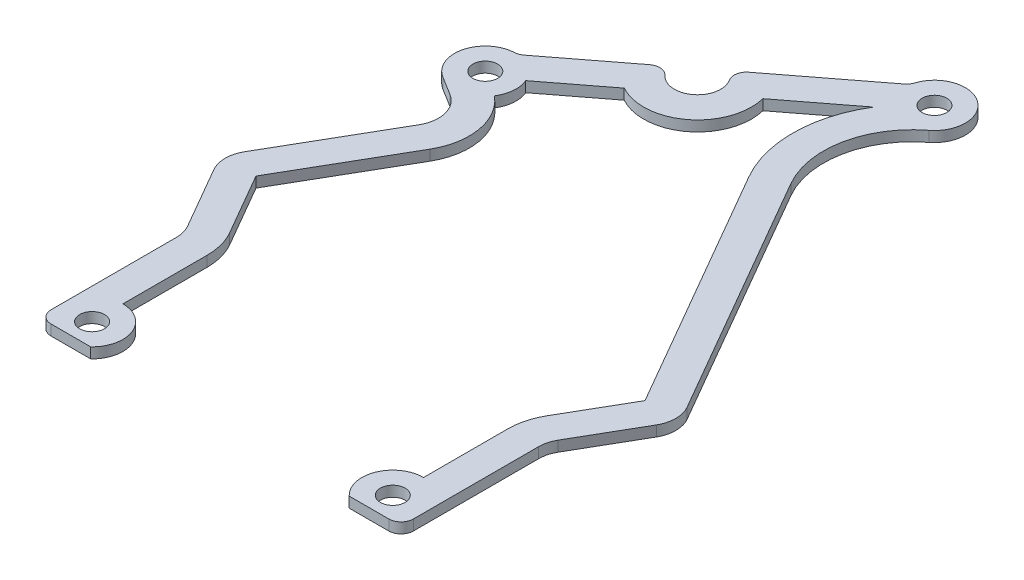
SolidWorks part; units mm, degrees
material "Alum Plate"
ref_plane "Front Plane" through (0, 0, 0) normal (0, 0, 1) x (1, 0, 0)
ref_plane "Top Plane" through (0, 0, 0) normal (0, 1, 0) x (1, 0, 0)
ref_plane "Right Plane" through (0, 0, 0) normal (1, 0, 0) x (0, 0, -1)
sketch "Top Layout" plane through (0, 0, 0) normal (0, 1, 0) x (1, 0, 0)
  line L0 (-114.046, -123.825) -> (-104.775, -123.825) construction
  line L1 (-104.775, -142.875) -> (-101.6, -142.875)
  line L2 (-104.775, -142.875) -> (-104.775, -104.775)
  line L3 (-104.775, -104.775) -> (-101.6, -104.775)
  line L4 (-101.6, -142.875) -> (-101.6, -104.775)
  line L5 (-104.775, -142.875) -> (-101.6, -104.775) construction
  line L6 (-104.775, -104.775) -> (-101.6, -142.875) construction
  line L7 (-19.05, -105.8164) -> (-101.6, -105.8164)
  line L8 (-19.05, -105.8164) -> (-19.05, -141.8336)
  line L9 (-19.05, -141.8336) -> (-101.6, -141.8336)
  line L10 (-101.6, -105.8164) -> (-101.6, -141.8336)
  line L11 (-19.05, -105.8164) -> (-101.6, -141.8336) construction
  line L12 (-19.05, -141.8336) -> (-101.6, -105.8164) construction
  line L13 (-133.096, -85.725) -> (-114.046, -85.725)
  line L14 (-133.096, -85.725) -> (-133.096, -161.925)
  line L15 (-133.096, -161.925) -> (-114.046, -161.925)
  line L16 (-114.046, -85.725) -> (-114.046, -161.925)
  line L17 (-133.096, -85.725) -> (-114.046, -161.925) construction
  line L18 (-133.096, -161.925) -> (-114.046, -85.725) construction
  line L19 (-104.775, -123.825) -> (0, -123.825) construction
  line L20 (0, -123.825) -> (0, 0) construction
  line L21 (-52.3528, -40.1717) -> (0, 0) construction
  line L22 (-70.6449, -16.3328) -> (-18.2922, 23.8388)
  line L23 (-34.0606, -64.0105) -> (18.2922, -23.8388)
  line L24 (-30.9251, 40.3023) -> (-122.2248, -29.7544)
  line L25 (-153.9748, -53.975) -> (-153.9748, -123.825)
  line L26 (-109.5248, -162.052) -> (109.5248, -162.052)
  line L27 (0, -162.052) -> (0, -123.825) construction
  line L28 (-109.5248, -162.052) -> (-109.5248, -20.0093) construction
  line L29 (-104.775, -142.875) -> (-104.775, -152.527)
  line L30 (-104.775, -152.527) -> (104.775, -152.527)
  line L31 (104.775, -104.775) -> (101.6, -104.775)
  line L32 (-144.4498, -73.025) -> (-109.5248, -73.025)
  line L33 (-144.4498, -73.025) -> (-144.4498, -123.825)
  line L34 (-144.4498, -123.825) -> (-109.5248, -123.825) construction
  line L35 (-109.5248, -73.025) -> (-109.5248, -162.052)
  line L36 (-144.4498, -73.025) -> (-109.5248, -123.825) construction
  line L37 (-144.4498, -123.825) -> (-109.5248, -73.025) construction
  line L38 (101.6, -142.875) -> (101.6, -104.775)
  line L39 (104.775, -142.875) -> (101.6, -142.875)
  line L40 (104.775, -142.875) -> (104.775, -104.775)
  line L41 (104.775, -142.875) -> (104.775, -152.527)
  line L42 (109.5248, -162.052) -> (109.5248, -20.0093) construction
  line L43 (30.9251, 40.3023) -> (122.2248, -29.7544)
  line L45 (19.05, -141.8336) -> (101.6, -141.8336)
  line L46 (101.6, -105.8164) -> (101.6, -141.8336)
  line L47 (19.05, -105.8164) -> (101.6, -105.8164)
  line L48 (19.05, -105.8164) -> (19.05, -141.8336)
  line L49 (133.096, -161.925) -> (114.046, -161.925)
  line L50 (114.046, -85.725) -> (114.046, -161.925)
  line L51 (133.096, -85.725) -> (114.046, -85.725)
  line L52 (133.096, -85.725) -> (133.096, -161.925)
  line L53 (144.4498, -123.825) -> (109.5248, -123.825) construction
  line L54 (109.5248, -73.025) -> (109.5248, -162.052)
  line L55 (144.4498, -73.025) -> (109.5248, -73.025)
  line L56 (144.4498, -73.025) -> (144.4498, -123.825)
  line L57 (-109.5248, -123.825) -> (-109.5248, -162.052) construction
  line L62 (-153.9748, -53.975) -> (-122.2248, -53.975)
  line L63 (-122.2248, -53.975) -> (-122.2248, -29.7544)
  line L64 (-144.4498, -123.825) -> (-153.9748, -123.825)
  line L65 (153.9748, -53.975) -> (153.9748, -123.825)
  line L66 (109.5248, -123.825) -> (109.5248, -162.052) construction
  line L67 (144.4498, -123.825) -> (153.9748, -123.825)
  line L68 (122.2248, -29.7544) -> (122.2248, -53.975)
  line L73 (-104.775, -104.775) -> (-104.775, -16.3647) construction
  line L74 (-95.25, -162.052) -> (-95.25, -9.0559) construction
  line L75 (-109.5248, -162.052) -> (-109.5248, -123.825) construction
  line L76 (109.5248, -162.052) -> (109.5248, -123.825) construction
  line L77 (122.2248, -53.975) -> (153.9748, -53.975)
  line L83 (104.775, -155.5496) -> (-104.775, -155.5496) construction
  line L88 (95.25, -162.052) -> (95.25, -9.0559) construction
  line L89 (104.775, -104.775) -> (104.775, -16.3647) construction
  line L92 (-104.775, -152.527) -> (-104.775, -162.052) construction
  line L93 (-14.605, -76.327) -> (14.605, -76.327)
  line L94 (-14.605, -76.327) -> (-14.605, -152.527)
  line L95 (-14.605, -152.527) -> (14.605, -152.527)
  line L96 (14.605, -76.327) -> (14.605, -152.527)
  line L97 (-14.605, -76.327) -> (14.605, -152.527) construction
  line L98 (-14.605, -152.527) -> (14.605, -76.327) construction
  line L99 (104.775, -152.527) -> (104.775, -162.052) construction
  line L100 (-19.05, -105.8164) -> (0, -105.8164) construction
  line L107 (0, -105.8164) -> (19.05, -105.8164) construction
  line L108 (104.775, -123.825) -> (114.046, -123.825) construction
  circle A0 centre (0, 0) radius 114.3
  circle A1 centre (0, 0) radius 6.35
  circle A2 centre (-52.3528, -40.1717) radius 17.8
  circle A3 centre (0, 0) radius 30.0482
  circle A4 centre (-52.3528, -40.1717) radius 30.0482
  arc A5 (-30.9251, 40.3023) -> (30.9251, 40.3023) centre (0, 0) cw
  point P2 (-103.1875, -123.825)
  point P7 (-60.325, -123.825)
  point P12 (-123.571, -123.825)
  point P30 (-126.9873, -98.425)
  point P35 (0, -114.427)
  point P53 (0, -152.527)
  dimension "D1" = 35.6
  dimension "D2" = 12.7
  dimension "D3" = 228.6
  dimension "D11" = 60.0964
  dimension "D12" = 50.8
  dimension "D14" = 52.5
  dimension "D4" = 3.175
  dimension "D5" = 19.05
  dimension "D6" = 76.2
  dimension "D7" = 82.55
  dimension "D8" = 38.1
  dimension "D9" = 104.775
  dimension "D10" = 18.0086
  dimension "D13" = 9.525
  dimension "D15" = 4.7498
  dimension "D16" = 9.525
  dimension "D17" = 9.652
  dimension "D18" = 50.8
  dimension "D19" = 12.446
  dimension "D20" = 65.9892
  dimension "D21" = 19.05
  dimension "D22" = 34.925
  dimension "D23" = 123.825
  dimension "D24" = 12.7
  dimension "D25" = 9.525
  dimension "D26" = 29.21
  dimension "D27" = 76.2
  dimension "D28" = 3.0226
sketch "Side Layout" plane through (0, 0, 0) normal (1, 0, 0) x (0, 0, -1)
  line L0 (0, -38.1) -> (0, 33.7344) construction
  line L1 (-114.3, -20.955) -> (114.3, -20.955)
  line L2 (-114.3, -20.955) -> (-114.3, -33.655)
  line L3 (-114.3, -33.655) -> (114.3, -33.655)
  line L4 (114.3, -20.955) -> (114.3, -33.655)
  line L5 (-114.3, -20.955) -> (114.3, -33.655) construction
  line L6 (-114.3, -33.655) -> (114.3, -20.955) construction
  line L7 (-9.525, -32.9406) -> (9.525, -32.9406)
  line L8 (-9.525, -32.9406) -> (-9.525, -38.1)
  line L9 (-9.525, -38.1) -> (9.525, -38.1)
  line L10 (9.525, -32.9406) -> (9.525, -38.1)
  line L11 (-9.525, -32.9406) -> (9.525, -38.1) construction
  line L12 (-9.525, -38.1) -> (9.525, -32.9406) construction
  line L13 (-11.9126, -29.3338) -> (11.9126, -29.3338)
  line L14 (-11.9126, -29.3338) -> (-11.9126, -32.9406)
  line L15 (-11.9126, -32.9406) -> (11.9126, -32.9406)
  line L16 (11.9126, -29.3338) -> (11.9126, -32.9406)
  line L17 (-11.9126, -29.3338) -> (11.9126, -32.9406) construction
  line L18 (-11.9126, -32.9406) -> (11.9126, -29.3338) construction
  line L19 (-6.35, -32.9406) -> (6.35, -32.9406)
  line L20 (-6.35, -32.9406) -> (-6.35, 33.7344)
  line L21 (-6.35, 33.7344) -> (6.35, 33.7344)
  line L22 (6.35, -32.9406) -> (6.35, 33.7344)
  line L23 (-6.35, -32.9406) -> (6.35, 33.7344) construction
  line L24 (-6.35, 33.7344) -> (6.35, -32.9406) construction
  line L25 (-162.052, 0) -> (-123.825, 0) construction
  line L26 (114.3, -33.655) -> (114.3, 0) construction
  line L27 (-142.875, 19.05) -> (-104.775, 19.05)
  line L28 (-40.1717, -9.525) -> (-40.1717, 5.4) construction
  line L29 (-142.875, 19.05) -> (-142.875, -19.05)
  line L30 (-142.875, -19.05) -> (-104.775, -19.05)
  line L31 (-104.775, 19.05) -> (-104.775, -19.05)
  line L32 (-142.875, 19.05) -> (-104.775, -19.05) construction
  line L33 (-142.875, -19.05) -> (-104.775, 19.05) construction
  line L34 (-130.175, -38.1) -> (-117.9516, -38.1) construction
  line L35 (-57.9717, -14.6) -> (-22.3717, -14.6)
  line L36 (-30.0482, -2.794) -> (30.0482, -2.794)
  line L37 (-30.0482, -2.794) -> (-30.0482, -20.955)
  line L38 (-30.0482, -20.955) -> (30.0482, -20.955)
  line L39 (30.0482, -2.794) -> (30.0482, -20.955)
  line L40 (-30.0482, -2.794) -> (30.0482, -20.955) construction
  line L41 (-30.0482, -20.955) -> (30.0482, -2.794) construction
  line L42 (-30.0482, -2.794) -> (-30.0482, 0) construction
  line L43 (-123.825, 0) -> (0, 0) construction
  line L44 (-57.9717, -14.6) -> (-57.9717, 25.4)
  line L45 (-57.9717, 25.4) -> (-22.3717, 25.4)
  line L46 (-22.3717, -14.6) -> (-22.3717, 25.4)
  line L47 (-19.05, 0) -> (19.05, 0)
  line L48 (-19.05, 0) -> (-19.05, -1.9812)
  line L49 (-19.05, -1.9812) -> (19.05, -1.9812)
  line L50 (19.05, 0) -> (19.05, -1.9812)
  line L51 (-19.05, 0) -> (19.05, -1.9812) construction
  line L52 (-19.05, -1.9812) -> (19.05, 0) construction
  line L53 (-70.2199, -3.175) -> (-10.1235, -3.175)
  line L54 (-70.2199, -3.175) -> (-70.2199, -15.875)
  line L55 (-70.2199, -15.875) -> (-10.1235, -15.875)
  line L56 (-10.1235, -3.175) -> (-10.1235, -15.875)
  line L57 (-70.2199, -3.175) -> (-10.1235, -15.875) construction
  line L58 (-70.2199, -15.875) -> (-10.1235, -3.175) construction
  line L59 (-40.1717, -9.525) -> (-40.1717, 0) construction
  line L60 (-57.9717, -14.6) -> (-22.3717, 25.4) construction
  line L61 (-57.9717, 25.4) -> (-22.3717, -14.6) construction
  line L62 (-22.3717, 0) -> (-57.9717, 0) construction
  line L63 (-137.8162, 0) -> (-123.825, -13.9912) construction
  line L64 (-139.065, 15.24) -> (-108.585, 15.24) construction
  line L65 (-139.065, 15.24) -> (-139.065, -15.24) construction
  line L66 (-139.065, -15.24) -> (-108.585, -15.24) construction
  line L67 (-108.585, 15.24) -> (-108.585, -15.24) construction
  line L68 (-139.065, 15.24) -> (-108.585, -15.24) construction
  line L69 (-139.065, -15.24) -> (-108.585, 15.24) construction
  line L70 (-137.8162, 0) -> (-123.825, 13.9912) construction
  line L71 (-123.825, -13.9912) -> (-109.8338, 0) construction
  line L72 (-123.825, 13.9912) -> (-109.8338, 0) construction
  line L73 (-137.8162, 0) -> (-109.8338, 0) construction
  line L74 (-123.825, -13.9912) -> (-123.825, 13.9912) construction
  line L75 (-6.35, 17.8594) -> (6.35, 17.8594)
  line L76 (114.3, 0) -> (-114.3, 0) construction
  line L77 (-22.3717, 19.05) -> (-6.35, 19.05) construction
  line L78 (-123.825, 38.1) -> (-97.9206, 38.1) construction
  line L79 (-19.05, -3.5814) -> (19.05, -3.5814)
  line L80 (-19.05, -3.5814) -> (-19.05, -1.9812)
  line L81 (-19.05, -1.9812) -> (19.05, -1.9812)
  line L82 (19.05, -3.5814) -> (19.05, -1.9812)
  line L83 (-19.05, -3.5814) -> (19.05, -1.9812) construction
  line L84 (-19.05, -1.9812) -> (19.05, -3.5814) construction
  line L85 (-8.7376, -16.7608) -> (8.7376, -16.7608)
  line L86 (-8.7376, -16.7608) -> (-8.7376, -29.3338)
  line L87 (-8.7376, -29.3338) -> (8.7376, -29.3338)
  line L88 (8.7376, -16.7608) -> (8.7376, -29.3338)
  line L89 (-8.7376, -16.7608) -> (8.7376, -29.3338) construction
  line L90 (-8.7376, -29.3338) -> (8.7376, -16.7608) construction
  line L91 (-8.7376, -3.5814) -> (8.7376, -3.5814)
  line L92 (-8.7376, -3.5814) -> (-8.7376, -16.1544)
  line L93 (-8.7376, -16.1544) -> (8.7376, -16.1544)
  line L94 (8.7376, -3.5814) -> (8.7376, -16.1544)
  line L95 (-8.7376, -3.5814) -> (8.7376, -16.1544) construction
  line L96 (-8.7376, -16.1544) -> (8.7376, -3.5814) construction
  circle A0 centre (-123.825, 0) radius 18.0086
  circle A1 centre (-123.825, 0) radius 38.1
  circle A2 centre (-139.065, 15.24) radius 1.905
  circle A3 centre (-108.585, 15.24) radius 1.905
  circle A4 centre (-108.585, -15.24) radius 1.905
  circle A5 centre (-139.065, -15.24) radius 1.905
  circle A6 centre (-137.8162, 0) radius 1.6002
  circle A7 centre (-123.825, 13.9912) radius 1.6002
  circle A8 centre (-109.8338, 0) radius 1.6002
  circle A9 centre (-123.825, -13.9912) radius 1.6002
  point P0 (0, -27.305)
  point P6 (0, -31.1372)
  point P7 (0, -35.5203)
  point P21 (0, 0.3969)
  point P32 (0, -11.8745)
  point P43 (0, -0.9906)
  point P55 (-40.1717, -9.525)
  point P72 (-40.1717, 5.4)
  point P88 (0, -23.0473)
  point P93 (0, -2.7813)
  point P102 (0, -9.8679)
  dimension "D17" = 3.81
  dimension "D18" = 3.2004
  dimension "D1" = 12.7
  dimension "D2" = 5.1594
  dimension "D3" = 19.05
  dimension "D4" = 3.6068
  dimension "D5" = 23.8252
  dimension "D6" = 12.7
  dimension "D7" = 18.161
  dimension "D8" = 1.9812
  dimension "D9" = 12.7
  dimension "D10" = 40
  dimension "D11" = 25.4
  dimension "D12" = 50.8
  dimension "D13" = 41.275
  dimension "D14" = 30.48
  dimension "D15" = 4.445
  dimension "D16" = 19.7866
  dimension "D19" = 15.875
  dimension "D20" = 6.35
  dimension "D21" = 38.1
  dimension "D22" = 1.6002
  dimension "D23" = 38.1
  dimension "D24" = 17.4752
  dimension "D25" = 12.573
ref_plane "Plane1" through (0, 25.4, 0) normal (0, 1, 0) x (1, 0, 0)
sketch "Sketch3" plane through (0, 25.4, 0) normal (0, 1, 0) x (1, 0, 0)
  line L0 (-104.775, -36.3747) -> (-30.9251, 20.2924)
  line L1 (-104.775, -104.775) -> (-104.775, -16.3647) construction
  line L2 (0, -200130.175) -> (0, 199882.0484) construction
  line L3 (-30.9251, 40.3023) -> (-122.2248, -29.7544) construction
  line L5 (-104.775, -36.3747) -> (-104.775, -77.6497)
  line L6 (-92.075, -77.6497) -> (-104.775, -77.6497)
  line L7 (30.9251, 20.2924) -> (104.775, -36.3747)
  line L8 (104.775, -77.6497) -> (92.075, -77.6497)
  line L9 (104.775, -36.3747) -> (104.775, -77.6497)
  line L11 (104.775, -104.775) -> (104.775, -16.3647) construction
  line L12 (30.9251, 40.3023) -> (122.2248, -29.7544) construction
  line L13 (92.075, -74.6536) -> (24.1423, -22.5271)
  line L14 (-32.2514, -66.3682) -> (20.1013, -26.1965)
  line L15 (-30.9251, 20.2924) -> (0, 44.022)
  line L16 (0, 44.022) -> (30.9251, 20.2924)
  line L17 (-92.075, -77.6497) -> (-92.075, -73.1917)
  line L19 (-92.075, -73.1917) -> (-52.3528, -73.1917)
  line L20 (92.075, -74.6536) -> (92.075, -77.6497)
  circle A0 centre (-52.3528, -40.1717) radius 17.8 construction
  circle A1 centre (-52.3528, -40.1717) radius 17.8
  circle A2 centre (0, 0) radius 6.35
  circle A3 centre (0, 0) radius 6.35 construction
  arc A4 (-52.3528, -73.1917) -> (-32.2514, -66.3682) centre (-52.3528, -40.1717) ccw
  arc A5 (20.1013, -26.1965) -> (24.1423, -22.5271) centre (0, 0) ccw
  arc A6 (30.9251, 20.2924) -> (-30.9251, 20.2924) centre (0, -20.01) ccw construction
  point P28 (0, 44.022)
  dimension "D1" = 33.02
  dimension "D5" = 50.8
  dimension "D2" = 41.275
  dimension "D3" = 34.925
  dimension "D4" = 12.7
  dimension "D6" = 38.1
ref_plane "Plane3" through (-104.775, 0, 0) normal (-1, 0, 0) x (0, 0, 1)
sketch "Sketch6" plane through (-104.775, 0, 0) normal (-1, 0, 0) x (0, 0, 1)
  line L0 (162.052, -25.4) -> (162.052, 25.4)
  line L1 (162.052, 25.4) -> (77.6497, 25.4)
  line L2 (36.3747, 25.4) -> (77.6497, 25.4) construction
  line L3 (147.7645, 11.1125) -> (162.052, 11.1125) construction
  line L4 (162.052, 0) -> (71.2997, 0) construction
  line L5 (77.6497, 25.4) -> (77.6497, 19.05)
  line L6 (77.6497, 19.05) -> (36.3747, 19.05)
  line L7 (36.3747, 19.05) -> (36.3747, 6.35)
  line L8 (36.3747, 6.35) -> (71.2997, 6.35)
  line L10 (99.6315, -3.175) -> (99.6315, 11.1125) construction
  line L11 (71.2997, -25.4) -> (162.052, -25.4)
  line L13 (71.2997, 6.35) -> (71.2997, -25.4)
  line L14 (152.527, -25.4) -> (152.527, 25.4) construction
  line L15 (99.6315, 11.1125) -> (99.6315, 25.4) construction
  line L16 (147.7645, 11.1125) -> (147.7645, 25.4) construction
  line L17 (94.869, -7.9375) -> (104.394, -7.9375) construction
  line L18 (94.869, -7.9375) -> (94.869, 25.4) construction
  line L19 (94.869, 25.4) -> (104.394, 25.4) construction
  line L20 (104.394, -7.9375) -> (104.394, 25.4) construction
  line L21 (94.869, -7.9375) -> (104.394, 25.4) construction
  line L22 (94.869, 25.4) -> (104.394, -7.9375) construction
  line L23 (147.7645, 11.1125) -> (147.7645, -3.175) construction
  line L24 (104.394, -7.9375) -> (123.825, -7.9375) construction
  line L25 (143.002, -7.9375) -> (152.527, -7.9375) construction
  line L26 (143.002, -7.9375) -> (143.002, 25.4) construction
  line L27 (143.002, 25.4) -> (152.527, 25.4) construction
  line L28 (152.527, -7.9375) -> (152.527, 25.4) construction
  line L29 (143.002, -7.9375) -> (152.527, 25.4) construction
  line L30 (143.002, 25.4) -> (152.527, -7.9375) construction
  line L31 (123.825, -7.9375) -> (152.527, -7.9375) construction
  line L32 (104.775, 19.05) -> (104.775, -19.05) construction
  line L34 (155.702, -25.4) -> (155.702, 25.4) construction
  circle A0 centre (109.8338, 0) radius 1.6002 construction
  circle A1 centre (123.825, 13.9912) radius 1.6002 construction
  circle A2 centre (137.8162, 0) radius 1.6002 construction
  circle A3 centre (123.825, -13.9912) radius 1.6002 construction
  circle A4 centre (109.8338, 0) radius 1.6002 construction
  circle A5 centre (123.825, 13.9912) radius 1.6002 construction
  circle A6 centre (137.8162, 0) radius 1.6002 construction
  circle A7 centre (123.825, -13.9912) radius 1.6002 construction
  circle A8 centre (123.825, 0) radius 18.0086 construction
  circle A9 centre (123.825, 0) radius 18.0086 construction
  circle A10 centre (123.825, 0) radius 9.525
  circle A11 centre (108.585, -15.24) radius 1.905 construction
  circle A12 centre (108.585, 15.24) radius 1.905 construction
  circle A13 centre (139.065, 15.24) radius 1.905 construction
  circle A14 centre (139.065, -15.24) radius 1.905 construction
  circle A15 centre (108.585, -15.24) radius 1.905
  circle A16 centre (108.585, 15.24) radius 1.905
  circle A17 centre (139.065, 15.24) radius 1.905
  circle A18 centre (139.065, -15.24) radius 1.905
  circle A19 centre (147.7645, 11.1125) radius 2.5527
  circle A26 centre (99.6315, 11.1125) radius 2.5527
  circle A27 centre (99.6315, -3.175) radius 2.5527
  circle A28 centre (147.7645, -3.175) radius 2.5527
  point P29 (0, 0)
  point P55 (99.6315, 8.7312)
  point P61 (147.7645, 8.7312)
  dimension "D4" = 19.05
  dimension "D7" = 5.1054
  dimension "D1" = 6.35
  dimension "D2" = 12.7
  dimension "D3" = 25.4
  dimension "D5" = 6.35
  dimension "D6" = 3.175
  dimension "D8" = 0.381
  dimension "D9" = 14.2875
  dimension "D10" = 9.525
  dimension "D12" = 33.3375
ref_plane "Plane4" through (0, 19.05, 0) normal (0, 1, 0) x (1, 0, 0)
sketch "Sketch12" plane through (0, 19.05, 0) normal (0, 1, 0) x (1, 0, 0)
  line L0 (-104.775, -77.6497) -> (-104.775, -36.3747)
  line L1 (-104.775, -36.3747) -> (-92.075, -36.3747)
  line L3 (-92.075, -36.3747) -> (-92.075, -77.6497)
  line L5 (-92.075, -77.6497) -> (-104.775, -77.6497)
  line L6 (-98.425, -77.6497) -> (-98.425, -63.3622) construction
  line L7 (-98.425, -63.3622) -> (-98.425, -50.6622) construction
  line L8 (-98.425, -50.6622) -> (-98.425, -36.3747) construction
  line L10 (-98.425, -36.3747) -> (-104.775, -36.3747) construction
  circle A0 centre (-98.425, -63.3622) radius 2.5527
  circle A1 centre (-98.425, -50.6622) radius 2.5527
  dimension "D2" = 5.1054
  dimension "D1" = 12.7
  dimension "D3" = 12.7
sketch "Sketch25" plane through (0, 25.4, 0) normal (0, 1, 0) x (1, 0, 0)
  line L0 (-104.775, -152.527) -> (104.775, -152.527)
  line L1 (-104.775, -152.527) -> (104.775, -152.527) construction
  line L2 (104.775, -152.527) -> (104.775, -162.052)
  line L3 (104.775, -162.052) -> (-104.775, -162.052)
  line L4 (-104.775, -162.052) -> (-104.775, -152.527)
ref_plane "Plane5" through (0, 0, 152.527) normal (0, 0, 1) x (1, 0, 0)
sketch "Sketch41" plane through (0, 0, 152.527) normal (0, 0, 1) x (1, 0, 0)
  line L0 (-104.775, -7.9375) -> (-104.775, 25.4) construction
  line L1 (-104.775, -7.9375) -> (-104.775, 12.7)
  line L2 (-104.775, -7.9375) -> (104.775, -7.9375)
  line L3 (104.775, -7.9375) -> (104.775, 12.7)
  line L4 (104.775, 25.4) -> (-104.775, 25.4)
  line L5 (0, -7.9375) -> (0, 25.4) construction
  line L6 (-104.775, 3.9624) -> (-100.0125, 3.9624) construction
  line L7 (-100.0125, 3.9624) -> (-100.0125, 25.4) construction
  line L8 (104.775, 3.9624) -> (100.0125, 3.9624) construction
  line L9 (100.0125, 3.9624) -> (100.0125, 25.4) construction
  line L10 (19.05, 20.6375) -> (23.8252, 20.6375) construction
  line L11 (19.05, 15.875) -> (78.5876, 15.875) construction
  line L12 (19.05, 15.875) -> (19.05, 25.4) construction
  line L13 (19.05, 25.4) -> (78.5876, 25.4) construction
  line L14 (78.5876, 15.875) -> (78.5876, 25.4) construction
  line L15 (19.05, 15.875) -> (78.5876, 25.4) construction
  line L16 (19.05, 25.4) -> (78.5876, 15.875) construction
  line L17 (23.8252, 20.6375) -> (38.1127, 20.6375) construction
  line L18 (38.1127, 20.6375) -> (52.4002, 20.6375) construction
  line L19 (52.4002, 20.6375) -> (66.6877, 20.6375) construction
  line L20 (-104.775, 25.4) -> (-112.395, 25.4)
  line L21 (-112.395, 25.4) -> (-112.395, 3.175)
  line L22 (-112.395, 3.175) -> (-109.5248, 3.175)
  line L23 (-109.5248, 3.175) -> (-109.5248, 12.7)
  line L24 (-109.5248, 12.7) -> (-104.775, 12.7)
  line L25 (-104.775, 12.7) -> (-104.775, 25.4) construction
  line L26 (104.775, 25.4) -> (112.395, 25.4)
  line L27 (112.395, 25.4) -> (112.395, 3.175)
  line L28 (112.395, 3.175) -> (109.5248, 3.175)
  line L29 (109.5248, 3.175) -> (109.5248, 12.7)
  line L30 (109.5248, 12.7) -> (104.775, 12.7)
  line L31 (104.775, 12.7) -> (104.775, 25.4) construction
  line L32 (-100.0125, 3.9624) -> (-87.3125, 3.9624) construction
  line L33 (-63.5, -1.5875) -> (0, -1.5875) construction
  line L34 (0, -1.5875) -> (63.5, -1.5875) construction
  line L35 (63.5, -1.5875) -> (63.5, -7.9375) construction
  circle A0 centre (-100.0125, 3.9624) radius 2.5527
  circle A1 centre (100.0125, 3.9624) radius 2.5527
  circle A2 centre (23.8252, 20.6375) radius 2.5527
  circle A3 centre (38.1127, 20.6375) radius 2.5527
  circle A4 centre (52.4002, 20.6375) radius 2.5527
  circle A5 centre (66.6877, 20.6375) radius 2.5527
  circle A6 centre (-66.6877, 20.6375) radius 2.5527
  circle A7 centre (-52.4002, 20.6375) radius 2.5527
  circle A8 centre (-38.1127, 20.6375) radius 2.5527
  circle A9 centre (-23.8252, 20.6375) radius 2.5527
  circle A10 centre (-87.3125, 3.9624) radius 2.5527
  circle A11 centre (87.3125, 3.9624) radius 2.5527
  circle A12 centre (-63.5, -1.5875) radius 2.5527
  circle A13 centre (63.5, -1.5875) radius 2.5527
  point P14 (48.8188, 20.6375)
  dimension "D3" = 5.1054
  dimension "D7" = 5.1054
  dimension "D1" = 21.4376
  dimension "D2" = 4.7625
  dimension "D4" = 9.525
  dimension "D5" = 59.5376
  dimension "D6" = 4.7752
  dimension "D8" = 14.2875
  dimension "D9" = 7.62
  dimension "D10" = 4.7498
  dimension "D11" = 12.7
  dimension "D12" = 9.525
  dimension "D13" = 19.05
  dimension "D14" = 12.7
  dimension "D15" = 6.35
  dimension "D16" = 63.5
sketch "Sketch44" plane through (0, 25.4, 0) normal (0, 1, 0) x (1, 0, 0)
  line L0 (73.8315, -147.7645) -> (73.8315, -152.527) construction
  line L1 (92.075, -74.6536) -> (92.075, -77.6497) construction
  line L2 (-92.075, -77.6497) -> (-92.075, -73.1917) construction
  line L3 (0, -123.825) -> (0, 0) construction
  line L4 (-92.075, -73.1917) -> (-52.3528, -73.1917) construction
  line L5 (-104.775, -104.775) -> (-104.775, -16.3647) construction
  line L6 (-32.2514, -66.3682) -> (20.1013, -26.1965) construction
  line L21 (-104.775, -68.1247) -> (-104.775, -152.527)
  line L22 (-104.775, -152.527) -> (104.775, -152.527)
  line L23 (104.775, -152.527) -> (104.775, -68.1247)
  line L34 (-104.775, -99.6315) -> (-100.0125, -99.6315) construction
  line L35 (-104.775, -147.7645) -> (-100.0125, -147.7645) construction
  line L36 (0, -152.527) -> (0, -35.6178) construction
  line L38 (30.969, -147.7645) -> (45.2565, -147.7645) construction
  line L39 (45.2565, -147.7645) -> (59.544, -147.7645) construction
  line L40 (59.544, -147.7645) -> (73.8315, -147.7645) construction
  line L41 (23.8252, -152.527) -> (30.969, -152.527) construction
  line L42 (104.775, -152.527) -> (-104.775, -152.527) construction
  line L43 (30.969, -152.527) -> (38.1127, -152.527) construction
  line L44 (30.969, -152.527) -> (30.969, -147.7645) construction
  line L45 (-92.075, -77.6497) -> (-104.775, -77.6497) construction
  line L48 (-35.1507, -62.5899) -> (-8.9743, -42.504) construction
  line L49 (-8.9743, -42.504) -> (17.2021, -22.4182) construction
  line L50 (45.5313, -32.9364) -> (87.3125, -64.9962) construction
  line L51 (92.075, -74.6536) -> (24.1423, -22.5271) construction
  line L52 (104.775, -77.6497) -> (92.075, -77.6497) construction
  line L79 (-104.775, -68.1247) -> (-92.075, -68.1247)
  line L80 (-92.075, -68.1247) -> (-92.075, -63.6667)
  line L85 (21.8118, -8.7328) -> (92.075, -62.6476)
  line L86 (-38.0499, -58.8115) -> (14.3028, -18.6398)
  line L87 (-92.075, -63.6667) -> (-52.3528, -63.6667)
  line L88 (92.075, -62.6476) -> (92.075, -68.1247)
  line L89 (92.075, -68.1247) -> (104.775, -68.1247)
  circle A0 centre (-73.8315, -147.7645) radius 2.5527
  circle A1 centre (-59.544, -147.7645) radius 2.5527
  circle A2 centre (-45.2565, -147.7645) radius 2.5527
  circle A3 centre (-30.969, -147.7645) radius 2.5527
  circle A17 centre (-100.0125, -99.6315) radius 2.5527
  circle A18 centre (-100.0125, -147.7645) radius 2.5527
  circle A19 centre (100.0125, -147.7645) radius 2.5527
  circle A20 centre (100.0125, -99.6315) radius 2.5527
  circle A21 centre (30.969, -147.7645) radius 2.5527
  circle A22 centre (45.2565, -147.7645) radius 2.5527
  circle A23 centre (59.544, -147.7645) radius 2.5527
  circle A24 centre (73.8315, -147.7645) radius 2.5527
  circle A25 centre (-87.3125, -68.4292) radius 4.7625 construction
  circle A26 centre (-35.1507, -62.5899) radius 4.7625 construction
  circle A27 centre (-8.9743, -42.504) radius 4.7625 construction
  circle A28 centre (17.2021, -22.4182) radius 4.7625 construction
  circle A29 centre (45.5313, -32.9364) radius 4.7625 construction
  circle A30 centre (87.3125, -64.9962) radius 4.7625 construction
  circle A32 centre (-87.3125, -68.4292) radius 2.5527
  circle A33 centre (-35.1507, -62.5899) radius 2.5527
  circle A34 centre (-8.9743, -42.504) radius 2.5527 construction
  circle A35 centre (17.2021, -22.4182) radius 2.5527
  circle A36 centre (45.5313, -32.9364) radius 2.5527
  circle A37 centre (87.3125, -64.9962) radius 2.5527
  circle A38 centre (-97.155, -85.2697) radius 7.62 construction
  circle A39 centre (97.155, -85.2697) radius 7.62 construction
  circle A40 centre (24.4294, -36.7543) radius 11.1125 construction
  arc A41 (20.1013, -26.1965) -> (24.1423, -22.5271) centre (0, 0) ccw construction
  circle A42 centre (-97.155, -85.2697) radius 2.5527
  circle A43 centre (24.4294, -36.7543) radius 2.5527
  circle A44 centre (97.155, -85.2697) radius 2.5527
  arc A56 (14.3028, -18.6398) -> (21.8118, -8.7328) centre (0, 0) ccw
  arc A57 (-52.3528, -63.6667) -> (-38.0499, -58.8115) centre (-52.3528, -40.1717) ccw
  point P4 (-104.775, -152.527)
  dimension "D2" = 5.1054
  dimension "D7" = 5.1054
  dimension "D8" = 15.24
  dimension "D3" = 9.525
  dimension "D9" = 9.525
  dimension "D11" = 22.225
  dimension "D4" = 4.7625
  dimension "D5" = 14.2875
  dimension "D6" = 9.525
  dimension "D1" = 4.7625
  dimension "D10" = 52.664
extrude "Top Plate Extrude-----------" add sketch "Sketch44" along normal blind 3.175
sketch "Sketch82" plane through (0, 28.575, 0) normal (0, 1, 0) x (1, 0, 0)
  line L0 (-52.3528, -63.6667) -> (-92.075, -63.6667) construction
  line L1 (-52.3528, -65.5717) -> (-52.3528, -63.6667) construction
  line L2 (-12.4467, -41.5667) -> (-13.6064, -40.0553) construction
  line L3 (14.3028, -18.6398) -> (-38.0499, -58.8115) construction
  line L4 (24.5175, -13.2101) -> (25.6772, -11.6988) construction
  line L5 (92.075, -62.6476) -> (21.8118, -8.7328) construction
  line L6 (58.2962, -39.1295) -> (59.4559, -37.6181) construction
  line L7 (21.4643, -9.5551) -> (21.8118, -8.7328)
  line L8 (21.8118, -8.7328) -> (22.2143, -9.0416)
  circle A0 centre (-52.3528, -65.5717) radius 4.7625
  circle A1 centre (-12.4467, -41.5667) radius 4.7625
  arc A2 (21.4643, -9.5551) -> (22.2143, -9.0416) centre (24.5175, -13.2101) ccw
  circle A3 centre (58.2962, -39.1295) radius 4.7625
  arc A4 (14.3028, -18.6398) -> (21.8118, -8.7328) centre (0, 0) ccw construction
  dimension "D1" = 9.525
  dimension "D2" = 1.905
  dimension "D3" = 30.8104
  dimension "D4" = 83.6926
  dimension "D5" = 41.1154
extrude "Cut-Extrude38" cut sketch "Sketch82" against normal up to surface (3.175 mm away) up to face at (-4.435, 25.4, 71.2837)
sketch "Sketch72" plane through (0, 25.4, 0) normal (0, 1, 0) x (1, 0, 0)
  line L0 (-104.775, -68.1247) -> (-104.775, -152.527) construction
  line L1 (-104.775, -152.527) -> (-109.5248, -152.527)
  line L2 (-104.775, -152.527) -> (-104.775, -135.0645)
  line L3 (-104.775, -135.0645) -> (-109.5248, -135.0645)
  line L4 (-109.5248, -152.527) -> (-109.5248, -135.0645)
  line L5 (-104.775, -152.527) -> (-109.5248, -135.0645) construction
  line L6 (-104.775, -135.0645) -> (-109.5248, -152.527) construction
  line L7 (-104.775, -152.527) -> (104.775, -152.527) construction
  line L8 (-77.0065, -152.527) -> (-73.8315, -147.7645) construction
  line L9 (-77.0065, -152.527) -> (-27.794, -152.527)
  line L10 (-77.0065, -152.527) -> (-77.0065, -155.5496)
  line L11 (-77.0065, -155.5496) -> (-27.794, -155.5496)
  line L12 (-27.794, -152.527) -> (-27.794, -155.5496)
  line L13 (-77.0065, -152.527) -> (-27.794, -155.5496) construction
  line L14 (-77.0065, -155.5496) -> (-27.794, -152.527) construction
  line L15 (-27.794, -152.527) -> (-30.969, -147.7645) construction
  line L16 (-77.0065, -152.527) -> (-77.0065, -147.7645) construction
  line L18 (-104.775, -93.5247) -> (-109.5248, -93.5247)
  line L19 (-104.775, -93.5247) -> (-104.775, -112.3315)
  line L20 (-104.775, -112.3315) -> (-109.5248, -112.3315)
  line L21 (-109.5248, -93.5247) -> (-109.5248, -112.3315)
  line L22 (-104.775, -93.5247) -> (-109.5248, -112.3315) construction
  line L23 (-104.775, -112.3315) -> (-109.5248, -93.5247) construction
  line L24 (0, -152.527) -> (-12.7, -152.527)
  line L25 (0, -152.527) -> (0, -155.5496)
  line L26 (0, -155.5496) -> (-12.7, -155.5496)
  line L27 (-12.7, -152.527) -> (-12.7, -155.5496)
  line L28 (0, -152.527) -> (-12.7, -155.5496) construction
  line L29 (0, -155.5496) -> (-12.7, -152.527) construction
  line L30 (-104.775, -68.1247) -> (-109.5248, -68.1247)
  line L31 (-104.775, -68.1247) -> (-104.775, -77.6497)
  line L32 (-104.775, -77.6497) -> (-109.5248, -77.6497)
  line L33 (-109.5248, -68.1247) -> (-109.5248, -77.6497)
  line L34 (-104.775, -68.1247) -> (-109.5248, -77.6497) construction
  line L35 (-104.775, -77.6497) -> (-109.5248, -68.1247) construction
  line L38 (-103.505, -155.5496) -> (-90.805, -155.5496)
  line L39 (-90.805, -152.527) -> (-90.805, -155.5496)
  line L40 (-103.505, -155.5496) -> (-103.505, -152.527)
  line L41 (-103.505, -155.5496) -> (-90.805, -152.527) construction
  line L42 (-103.505, -152.527) -> (-90.805, -152.527)
  line L43 (-77.0065, -147.7645) -> (-73.8315, -147.7645) construction
  line L44 (-103.505, -152.527) -> (-101.5221, -149.823) construction
  circle A0 centre (-100.0125, -147.7645) radius 2.5527 construction
  circle A1 centre (-73.8315, -147.7645) radius 2.5527 construction
  circle A2 centre (-30.969, -147.7645) radius 2.5527 construction
  point P4 (-107.1499, -143.7958)
  point P5 (-100.0125, -147.7645)
  point P16 (-52.4002, -154.0383)
  point P18 (-97.155, -154.0383)
  point P25 (-107.1499, -102.9281)
  point P34 (-6.35, -154.0383)
  point P39 (-107.1499, -72.8872)
  dimension "D1" = 4.7498
  dimension "D2" = 12.7
  dimension "D3" = 12.7
  dimension "D4" = 12.7
  dimension "D5" = 9.525
  dimension "D6" = 15.875
  dimension "D7" = 12.7
  dimension "D8" = 3.175
  dimension "D9" = 1.27
  dimension "D10" = 3.0226
extrude "Boss-Extrude27" add sketch "Sketch72" along normal through all
mirror "Mirror22" about plane through (0, 0, 0) normal (1, 0, 0) of "Boss-Extrude27"
sketch "Sketch86" plane through (0, 28.575, 0) normal (0, 1, 0) x (1, 0, 0)
  circle A0 centre (87.3125, -64.9962) radius 6.35
  circle A3 centre (17.2021, -22.4182) radius 6.35
  circle A4 centre (45.5313, -32.9364) radius 6.35
  circle A5 centre (-35.1507, -62.5899) radius 6.35
  circle A6 centre (-87.3125, -68.4292) radius 6.35
  circle A7 centre (87.3125, -64.9962) radius 2.5527 construction
  circle A8 centre (45.5313, -32.9364) radius 2.5527 construction
  circle A9 centre (17.2021, -22.4182) radius 2.5527 construction
  circle A10 centre (-35.1507, -62.5899) radius 2.5527 construction
  circle A11 centre (-87.3125, -68.4292) radius 2.5527 construction
  circle A12 centre (87.3125, -64.9962) radius 2.5527
  circle A13 centre (45.5313, -32.9364) radius 2.5527
  circle A14 centre (17.2021, -22.4182) radius 2.5527
  circle A15 centre (-35.1507, -62.5899) radius 2.5527
  circle A16 centre (-87.3125, -68.4292) radius 2.5527
  dimension "D1" = 12.7
extrude "Boss-Extrude31" add sketch "Sketch86" against normal through all
ref_plane "Plane8" through (0, 28.829, 0) normal (0, 1, 0) x (1, 0, 0)
sketch "Sketch87" plane through (0, 28.829, 0) normal (0, 1, 0) x (1, 0, 0)
  line L0 (0, -123.825) -> (0, 0) construction
  line L1 (-25.4, -66.802) -> (25.4, -66.802)
  line L2 (-25.4, -66.802) -> (-25.4, -143.002) construction
  line L3 (-25.4, -143.002) -> (25.4, -143.002)
  line L4 (25.4, -66.802) -> (25.4, -143.002) construction
  line L5 (-25.4, -66.802) -> (25.4, -143.002) construction
  line L6 (-25.4, -143.002) -> (25.4, -66.802) construction
  line L7 (-104.775, -152.527) -> (104.775, -152.527) construction
  line L8 (-25.4, -71.5645) -> (-20.6375, -71.5645) construction
  line L9 (-20.6375, -71.5645) -> (-20.6375, -66.802) construction
  line L10 (20.6375, -66.802) -> (20.6375, -71.5645) construction
  line L11 (20.6375, -71.5645) -> (25.4, -71.5645) construction
  line L12 (20.6375, -143.002) -> (20.6375, -138.2395) construction
  line L13 (20.6375, -138.2395) -> (25.4, -138.2395) construction
  line L14 (-20.6375, -143.002) -> (-20.6375, -138.2395) construction
  line L15 (-20.6375, -138.2395) -> (-25.4, -138.2395) construction
  line L16 (-25.4, -143.002) -> (-47.397, -104.902)
  line L17 (-47.397, -104.902) -> (-25.4, -66.802)
  line L18 (25.4, -66.802) -> (47.397, -104.902)
  line L19 (47.397, -104.902) -> (25.4, -143.002)
  circle A0 centre (-20.6375, -71.5645) radius 2.5527
  circle A1 centre (20.6375, -71.5645) radius 2.5527
  circle A3 centre (-20.6375, -138.2395) radius 2.5527
  circle A4 centre (20.6375, -138.2395) radius 2.5527
  point P0 (0, -104.902)
  dimension "D5" = 5.1054
  dimension "D1" = 50.8
  dimension "D2" = 9.525
  dimension "D3" = 76.2
  dimension "D4" = 4.7625
  dimension "D6" = 120
sketch "Sketch111" plane through (0, 28.575, 0) normal (0, 1, 0) x (1, 0, 0)
  line L0 (-109.5248, -77.6497) -> (-104.775, -77.6497) construction
  line L1 (-109.5248, -67.8707) -> (-91.7575, -67.8707)
  line L2 (-109.5248, -67.8707) -> (-109.5248, -77.9672)
  line L3 (-109.5248, -77.9672) -> (-91.7575, -77.9672)
  line L4 (-91.7575, -67.8707) -> (-91.7575, -77.9672)
  line L5 (-109.5248, -67.8707) -> (-91.7575, -77.9672) construction
  line L6 (-109.5248, -77.9672) -> (-91.7575, -67.8707) construction
  line L7 (109.5248, -67.8707) -> (91.7575, -67.8707)
  line L8 (109.5248, -67.8707) -> (109.5248, -77.9672)
  line L9 (109.5248, -77.9672) -> (91.7575, -77.9672)
  line L10 (91.7575, -67.8707) -> (91.7575, -77.9672)
  line L11 (109.5248, -67.8707) -> (91.7575, -77.9672) construction
  line L12 (109.5248, -77.9672) -> (91.7575, -67.8707) construction
  line L13 (-93.6552, -68.1247) -> (-109.5248, -68.1247) construction
  line L14 (-109.5248, -68.1247) -> (-109.5248, -77.6497) construction
  line L15 (109.5248, -68.1247) -> (109.5248, -77.6497) construction
  line L16 (-104.775, -104.775) -> (-104.775, -16.3647) construction
  point P4 (-100.6411, -72.9189)
  point P10 (100.6411, -72.9189)
  dimension "D1" = 13.0175
  dimension "D2" = 0.3175
  dimension "D3" = 0.254
extrude "Cut-Extrude57" cut sketch "Sketch111" against normal through all
sketch "Sketch92" plane through (0, 28.575, 0) normal (0, 1, 0) x (1, 0, 0)
  line L0 (-109.5248, -93.5247) -> (-109.5248, -112.3315) construction
  line L1 (-109.5248, -93.6517) -> (-104.665, -93.6517)
  line L2 (-109.5248, -93.6517) -> (-109.5248, -77.9672)
  line L3 (-109.5248, -77.9672) -> (-104.665, -77.9672)
  line L4 (-104.665, -93.6517) -> (-104.665, -77.9672)
  line L5 (-109.5248, -93.6517) -> (-104.665, -77.9672) construction
  line L6 (-109.5248, -77.9672) -> (-104.665, -93.6517) construction
  line L7 (-109.5248, -135.0645) -> (-109.5248, -152.527) construction
  line L8 (-109.5248, -135.1915) -> (-104.648, -135.1915)
  line L9 (-109.5248, -135.1915) -> (-109.5248, -112.2045)
  line L10 (-109.5248, -112.2045) -> (-104.648, -112.2045)
  line L11 (-104.648, -135.1915) -> (-104.648, -112.2045)
  line L12 (-109.5248, -135.1915) -> (-104.648, -112.2045) construction
  line L13 (-109.5248, -112.2045) -> (-104.648, -135.1915) construction
  line L14 (-103.505, -155.5496) -> (-90.805, -155.5496) construction
  line L15 (-103.378, -155.5496) -> (-109.5248, -155.5496)
  line L16 (-103.378, -155.5496) -> (-103.378, -152.4)
  line L17 (-103.378, -152.4) -> (-109.5248, -152.4)
  line L18 (-109.5248, -155.5496) -> (-109.5248, -152.4)
  line L19 (-103.378, -155.5496) -> (-109.5248, -152.4) construction
  line L20 (-103.378, -152.4) -> (-109.5248, -155.5496) construction
  line L21 (-77.0065, -155.5496) -> (-27.794, -155.5496) construction
  line L22 (-90.8812, -155.5496) -> (-76.9302, -155.5496)
  line L23 (-90.8812, -155.5496) -> (-90.8812, -152.4)
  line L24 (-90.8812, -152.4) -> (-76.9302, -152.4)
  line L25 (-76.9302, -155.5496) -> (-76.9302, -152.4)
  line L26 (-90.8812, -155.5496) -> (-76.9302, -152.4) construction
  line L27 (-90.8812, -152.4) -> (-76.9302, -155.5496) construction
  line L28 (-27.8702, -155.5496) -> (-12.6238, -155.5496)
  line L29 (-27.8702, -155.5496) -> (-27.8702, -152.4)
  line L30 (-27.8702, -152.4) -> (-12.6238, -152.4)
  line L31 (-12.6238, -155.5496) -> (-12.6238, -152.4)
  line L32 (-27.8702, -155.5496) -> (-12.6238, -152.4) construction
  line L33 (-27.8702, -152.4) -> (-12.6238, -155.5496) construction
  line L34 (-104.775, -77.9672) -> (-91.7575, -77.9672) construction
  line L35 (-104.775, -85.7459) -> (-104.665, -85.8094) construction
  line L36 (-104.775, -77.9672) -> (-104.775, -93.5247) construction
  line L37 (-104.775, -93.5247) -> (-104.775, -93.6517) construction
  line L38 (-104.775, -112.3315) -> (-104.775, -112.2045) construction
  line L39 (-104.775, -123.698) -> (-104.648, -123.698) construction
  line L40 (-104.775, -112.3315) -> (-104.775, -135.0645) construction
  line L41 (-104.775, -135.0645) -> (-104.775, -135.1915) construction
  line L42 (-103.505, -152.527) -> (-103.505, -152.4) construction
  line L43 (-103.505, -152.527) -> (-103.378, -152.527) construction
  line L44 (-90.8812, -152.527) -> (-90.805, -152.527) construction
  line L45 (-83.9057, -152.527) -> (-83.9057, -152.4) construction
  line L46 (-90.805, -152.527) -> (-77.0065, -152.527) construction
  line L47 (-77.0065, -152.527) -> (-76.9302, -152.527) construction
  line L48 (-27.794, -152.527) -> (-27.8702, -152.527) construction
  line L49 (-20.247, -152.527) -> (-20.247, -152.4) construction
  line L50 (-27.794, -152.527) -> (-12.7, -152.527) construction
  line L51 (-12.7, -152.527) -> (-12.6238, -152.527) construction
  line L52 (-12.7, -155.5496) -> (12.7, -155.5496) construction
  point P4 (-107.0949, -85.8094)
  point P11 (-107.0864, -123.698)
  point P18 (-106.4514, -153.9748)
  point P25 (-83.9057, -153.9748)
  point P30 (-20.247, -153.9748)
  dimension "D1" = 0.0762
  dimension "D2" = 0.127
extrude "Cut-Extrude44" cut sketch "Sketch92" against normal through all
mirror "Mirror26" about plane through (0, 0, 0) normal (1, 0, 0) of "Cut-Extrude44"
sketch "Sketch95" plane through (0, 28.575, 0) normal (0, 1, 0) x (1, 0, 0)
  line L0 (-25.4, -104.902) -> (-23.495, -104.902) construction
  line L1 (-23.495, -141.097) -> (23.495, -141.097)
  line L2 (-23.495, -141.097) -> (-23.495, -68.707) construction
  line L3 (-23.495, -68.707) -> (23.495, -68.707)
  line L4 (23.495, -141.097) -> (23.495, -68.707) construction
  line L5 (-23.495, -141.097) -> (23.495, -68.707) construction
  line L6 (-23.495, -68.707) -> (23.495, -141.097) construction
  line L7 (-25.4, -66.802) -> (-25.4, -143.002) construction
  line L8 (23.495, -104.902) -> (25.4, -104.902) construction
  line L9 (25.4, -66.802) -> (25.4, -143.002) construction
  line L10 (0, -143.002) -> (0, -141.097) construction
  line L11 (-25.4, -143.002) -> (25.4, -143.002) construction
  line L12 (0, -68.707) -> (0, -66.802) construction
  line L13 (-25.4, -66.802) -> (25.4, -66.802) construction
  line L14 (-23.495, -68.707) -> (-44.3922, -104.902)
  line L15 (-44.3922, -104.902) -> (-23.495, -141.097)
  line L16 (23.495, -141.097) -> (44.3922, -104.902)
  line L17 (44.3922, -104.902) -> (23.495, -68.707)
  line L18 (-47.397, -104.902) -> (-25.4, -66.802) construction
  circle A0 centre (-20.6375, -71.5645) radius 6.35
  circle A1 centre (20.6375, -71.5645) radius 6.35
  circle A2 centre (-20.6375, -138.2395) radius 6.35
  circle A3 centre (20.6375, -138.2395) radius 6.35
  circle A4 centre (-20.6375, -71.5645) radius 2.5527
  circle A5 centre (20.6375, -71.5645) radius 2.5527
  circle A6 centre (20.6375, -138.2395) radius 2.5527
  circle A7 centre (-20.6375, -138.2395) radius 2.5527
  point P12 (0, -104.902)
  dimension "D1" = 12.7
  dimension "D3" = 5.1054
  dimension "D2" = 1.905
extrude "Cut-Extrude47" cut sketch "Sketch95" against normal blind 25.4 contours A3 L4 A1 L3 A0 L2 A2 L1 | A4 | A5 | A6 | A7 region at (0, 28.575, 104.902) region at (-20.6375, 28.575, 71.5645) region at (20.6375, 28.575, 71.5645) region at (20.6375, 28.575, 138.2395) region at (-20.6375, 28.575, 138.2395)
sketch "Sketch99" plane through (0, 28.575, 0) normal (0, 1, 0) x (1, 0, 0)
  line L0 (0, -68.707) -> (0, -60.1955) construction
  line L1 (-14.9668, -68.707) -> (14.9668, -68.707) construction
  line L2 (0, -60.1955) -> (-1.8339, -60.1955) construction
  circle A0 centre (-1.8339, -60.1955) radius 3.175
  dimension "D2" = 6.35
  dimension "D1" = 8.5115
  dimension "D3" = 1.8339
extrude "Cut-Extrude50" cut sketch "Sketch99" against normal through all
sketch "Sketch112" plane through (0, 28.575, 0) normal (0, 1, 0) x (1, 0, 0)
  line L0 (-26.5222, -135.8537) -> (-24.619, -139.1503)
  line L1 (-24.619, -139.1503) -> (-24.619, -152.4)
  line L2 (-12.6238, -152.4) -> (-27.8702, -152.4) construction
  line L3 (-24.619, -152.4) -> (-24.619, -155.5496)
  line L4 (-24.619, -155.5496) -> (24.619, -155.5496)
  line L5 (24.619, -155.5496) -> (24.619, -152.4)
  line L6 (12.6238, -152.4) -> (27.8702, -152.4) construction
  line L7 (24.619, -152.4) -> (24.619, -139.1503)
  line L8 (24.619, -139.1503) -> (26.5222, -135.8537)
  line L9 (26.5222, -135.8537) -> (26.5222, -131.8895)
  line L10 (26.5222, -131.8895) -> (-26.5222, -131.8895)
  line L11 (-26.5222, -131.8895) -> (-26.5222, -135.8537)
  line L12 (-12.6238, -155.5496) -> (12.6238, -155.5496) construction
  line L13 (-44.3922, -104.902) -> (-26.5222, -135.8537) construction
  line L14 (26.5222, -135.8537) -> (44.3922, -104.902) construction
  arc A0 (-14.9668, -141.097) -> (-26.5222, -135.8537) centre (-20.6375, -138.2395) ccw construction
  circle A1 centre (-30.969, -147.7645) radius 2.5527 construction
  dimension "D1" = 6.35
extrude "Cut-Extrude58" cut sketch "Sketch112" against normal through all
sketch "Sketch115" plane through (0, 28.575, 0) normal (0, 1, 0) x (1, 0, 0)
  line L1 (-91.7575, -67.8707) -> (-93.6379, -67.8707)
  line L2 (-91.7575, -67.8707) -> (-91.7575, -63.8944)
  line L3 (-91.7575, -63.6667) -> (-93.6379, -63.6667)
  line L4 (-93.6379, -67.8707) -> (-93.6379, -63.6667)
  line L5 (-91.7575, -67.8707) -> (-93.6379, -63.6667) construction
  line L6 (-91.7575, -63.6667) -> (-93.6379, -67.8707) construction
  line L7 (-91.5126, -63.6667) -> (-91.7575, -63.6667)
  line L8 (-91.7575, -63.8944) -> (-91.7575, -63.6667) construction
  line L9 (-91.7575, -67.8707) -> (-93.6379, -67.8707) construction
  line L11 (91.7575, -67.8707) -> (93.6625, -67.8707)
  line L12 (91.7575, -67.8707) -> (91.7575, -60.4614)
  line L13 (91.7575, -60.4614) -> (93.6625, -60.4614)
  line L14 (93.6625, -67.8707) -> (93.6625, -60.4614)
  line L15 (91.7575, -67.8707) -> (93.6625, -60.4614) construction
  line L16 (91.7575, -60.4614) -> (93.6625, -67.8707) construction
  arc A0 (-92.075, -64.229) -> (-93.6379, -67.8707) centre (-87.3125, -68.4292) ccw construction
  arc A1 (-91.5126, -63.6667) -> (-91.7575, -63.8944) centre (-87.3125, -68.4292) ccw
  arc A2 (92.9747, -67.8707) -> (86.8795, -58.661) centre (87.3125, -64.9962) ccw construction
  point P4 (-92.6977, -65.7687)
  point P22 (92.71, -64.1661)
extrude "Cut-Extrude60" cut sketch "Sketch115" against normal through all
fillet "Fillet5" radius 2.54 8 edges at (-44.3922, 26.9875, 104.902) (44.3922, 26.9875, 104.902) (26.5222, 26.9875, 73.9503) (14.9668, 26.9875, 68.707) (-14.9668, 26.9875, 68.707) (-26.5222, 26.9875, 73.9503) (24.619, 26.9875, 139.1503) (-24.619, 26.9875, 139.1503)
fillet "Fillet6" radius 2.54 2 edges at (-91.7575, 26.9875, 63.8944) (91.7575, 26.9875, 60.4614)
fillet "Fillet7" radius 2.54 17 edges at (86.8795, 26.9875, 58.661) (62.9188, 26.9875, 40.2753) (55.993, 26.9875, 34.961) (51.7627, 26.9875, 31.7149) (45.0984, 26.9875, 26.6012) (29.1401, 26.9875, 14.356) (17.1412, 26.9875, 16.0685) (10.9707, 26.9875, 21.1967) (-10.1435, 26.9875, 37.3981) (-17.0693, 26.9875, 42.7125) (-34.7177, 26.9875, 56.2546) (-41.2683, 26.9875, 60.8876) (-48.1715, 26.9875, 63.2916) (-56.7177, 26.9875, 63.6667) (-83.1124, 26.9875, 63.6667) (104.665, 26.9875, 77.9672) (-104.665, 26.9875, 77.9672)
fillet "Fillet8" radius 1.905 1 edges at (19.7857, 26.9875, 12.6705)
sketch "Sketch113" plane through (0, 28.575, 0) normal (0, 1, 0) x (1, 0, 0)
  circle A0 centre (-91.7575, -77.9672) radius 0.508
  circle A1 centre (-104.665, -93.6517) radius 0.508
  circle A2 centre (-104.648, -112.2045) radius 0.508
  circle A3 centre (-104.648, -135.1915) radius 0.508
  circle A4 centre (-103.378, -152.4) radius 0.508
  circle A5 centre (-90.8812, -152.4) radius 0.508
  circle A6 centre (-76.9302, -152.4) radius 0.508
  circle A7 centre (-27.8702, -152.4) radius 0.508
  dimension "D1" = 1.016
extrude "Cut-Extrude59" cut sketch "Sketch113" against normal through all
fillet "Fillet43" radius 0.635 16 edges at (-92.2655, 26.9875, 77.9672) (-91.7575, 26.9875, 77.4592) (-104.665, 26.9875, 93.1437) (-105.173, 26.9875, 93.6517) (-105.156, 26.9875, 112.2045) (-104.648, 26.9875, 112.7125) (-105.156, 26.9875, 135.1915) (-104.648, 26.9875, 134.6835) (-103.378, 26.9875, 152.908) (-103.886, 26.9875, 152.4) (-90.8812, 26.9875, 152.908) (-90.3732, 26.9875, 152.4) (-76.9302, 26.9875, 152.908) (-77.4382, 26.9875, 152.4) (-27.8702, 26.9875, 152.908) (-27.3622, 26.9875, 152.4)
mirror "Mirror29" about plane through (0, 0, 0) normal (1, 0, 0) of "Fillet43", "Cut-Extrude59"
sketch "Sketch116" plane through (0, 28.575, 0) normal (0, 1, 0) x (1, 0, 0)
  line L0 (-23.495, -141.097) -> (23.495, -68.707) construction
  line L1 (-25.4, -66.802) -> (25.4, -66.802)
  line L2 (-25.4, -66.802) -> (-25.4, -143.002) construction
  line L3 (-25.4, -143.002) -> (25.4, -143.002) construction
  line L4 (25.4, -66.802) -> (25.4, -143.002) construction
  line L5 (-25.4, -66.802) -> (25.4, -143.002) construction
  line L6 (-25.4, -143.002) -> (25.4, -66.802) construction
  line L7 (-37.319, -122.3578) -> (-47.397, -104.902)
  line L8 (-47.397, -104.902) -> (-25.4, -66.802)
  line L9 (25.4, -66.802) -> (47.397, -104.902)
  line L10 (47.397, -104.902) -> (37.3189, -122.3578)
  line L11 (-23.495, -68.707) -> (-44.3922, -104.902) construction
  line L12 (-25.4, -71.5645) -> (-20.6375, -71.5645) construction
  line L13 (-20.6375, -71.5645) -> (-20.6375, -66.802) construction
  line L14 (-25.4, -143.002) -> (-37.319, -143.002) construction
  line L15 (-37.319, -143.002) -> (-37.319, -152.4)
  line L16 (-37.319, -152.4) -> (-12.4206, -152.4)
  line L17 (-12.4206, -152.4) -> (-12.4206, -155.5496)
  line L18 (-12.4206, -155.5496) -> (12.4206, -155.5496)
  line L19 (12.4206, -155.5496) -> (12.4206, -152.4)
  line L20 (12.4206, -152.4) -> (37.3189, -152.4)
  line L21 (37.3189, -152.4) -> (37.3189, -143.002)
  line L22 (37.3189, -143.002) -> (25.4, -143.002) construction
  line L23 (-27.8702, -152.4) -> (-12.6238, -152.4) construction
  line L24 (-76.9302, -155.5496) -> (-27.8702, -155.5496) construction
  line L25 (-12.6238, -155.5496) -> (-12.6238, -152.4) construction
  line L26 (-37.319, -143.002) -> (-37.319, -122.3578)
  line L27 (37.3189, -143.002) -> (37.3189, -122.3578)
  line L28 (-25.4, -143.002) -> (-37.319, -122.3578) construction
  line L29 (37.3189, -122.3578) -> (25.4, -143.002) construction
  line L30 (-44.3922, -104.902) -> (-23.495, -141.097) construction
  circle A0 centre (-30.969, -147.7645) radius 2.5527 construction
  circle A1 centre (30.969, -147.7645) radius 2.5527 construction
  circle A2 centre (30.969, -147.7645) radius 2.5527
  circle A3 centre (-30.969, -147.7645) radius 2.5527
  circle A4 centre (20.6375, -71.5645) radius 2.5527 construction
  circle A5 centre (-20.6375, -71.5645) radius 2.5527 construction
  circle A6 centre (20.6375, -71.5645) radius 2.5527
  circle A7 centre (-20.6375, -71.5645) radius 2.5527
  point P0 (0, -104.902)
  dimension "D1" = 76.2
  dimension "D2" = 6.35
  dimension "D3" = 0.2032
extrude "Boss-Extrude32" add sketch "Sketch116" along normal blind 3.175 from offset 2.159 separate body
sketch "Sketch117" plane through (0, 28.575, 0) normal (0, 1, 0) x (1, 0, 0)
  line L0 (24.4294, -36.7543) -> (23.1263, -40.3346) construction
  line L1 (26.8282, -37.6274) -> (25.5251, -41.2076)
  line L2 (22.0307, -35.8813) -> (20.7276, -39.4615)
  line L3 (0, 0) -> (0, -66.8162) construction
  line L5 (-1.8339, -60.1955) -> (-1.8339, -61.783) construction
  line L6 (1.3411, -60.1955) -> (1.3411, -61.783)
  line L7 (-5.0089, -60.1955) -> (-5.0089, -61.783)
  arc A0 (26.8282, -37.6274) -> (22.0307, -35.8813) centre (24.4294, -36.7543) ccw
  arc A1 (20.7276, -39.4615) -> (25.5251, -41.2076) centre (23.1263, -40.3346) ccw
  circle A2 centre (24.4294, -36.7543) radius 2.5527 construction
  arc A3 (1.3411, -60.1955) -> (-5.0089, -60.1955) centre (-1.8339, -60.1955) ccw
  arc A4 (-5.0089, -61.783) -> (1.3411, -61.783) centre (-1.8339, -61.783) ccw
  circle A5 centre (-1.8339, -60.1955) radius 3.175 construction
  point P3 (23.7779, -38.5445)
  point P15 (-1.8339, -60.9892)
  dimension "D1" = 3.81
  dimension "D2" = 20
  dimension "D3" = 1.5875
extrude "Cut-Extrude61" cut sketch "Sketch117" against normal through all
sketch "Sketch118" plane through (0, 30.734, 0) normal (0, 1, 0) x (1, 0, 0)
  line L0 (-5.0089, -60.1955) -> (-5.0089, -61.783) construction
  line L1 (1.3411, -61.783) -> (1.3411, -60.1955) construction
  line L2 (-5.0089, -60.1955) -> (-5.0089, -61.783)
  line L3 (1.3411, -61.783) -> (1.3411, -60.1955)
  line L4 (10.2805, -21.7263) -> (-7.8349, -35.6267) construction
  line L5 (-19.3779, -44.484) -> (-34.0275, -55.7251) construction
  line L6 (10.2805, -21.7263) -> (-7.8349, -35.6267)
  line L7 (-19.3779, -44.484) -> (-34.0275, -55.7251)
  line L8 (25.4, -66.802) -> (16.3569, -51.1389)
  line L9 (25.4, -66.802) -> (-25.4, -66.802)
  line L10 (-25.4, -66.802) -> (-29.3497, -73.6431)
  line L11 (-25.4, -66.802) -> (-47.397, -104.902) construction
  line L12 (-29.3497, -73.6431) -> (-38.4904, -67.9907)
  line L13 (47.397, -104.902) -> (25.4, -66.802) construction
  line L14 (19.2887, -28.8211) -> (-39648.3783, -30466.8925) construction
  line L15 (-20.6375, -71.5645) -> (-35.1507, -62.5899) construction
  circle A0 centre (17.2021, -22.4182) radius 2.5527 construction
  arc A1 (1.3411, -60.1955) -> (-5.0089, -60.1955) centre (-1.8339, -60.1955) ccw construction
  arc A2 (-5.0089, -61.783) -> (1.3411, -61.783) centre (-1.8339, -61.783) ccw construction
  circle A3 centre (-35.1507, -62.5899) radius 2.5527 construction
  circle A4 centre (17.2021, -22.4182) radius 2.5527
  arc A5 (1.3411, -60.1955) -> (-5.0089, -60.1955) centre (-1.8339, -60.1955) ccw
  arc A6 (-5.0089, -61.783) -> (1.3411, -61.783) centre (-1.8339, -61.783) ccw
  circle A7 centre (-35.1507, -62.5899) radius 2.5527
  arc A8 (10.2805, -21.7263) -> (11.1536, -20.4846) centre (8.7342, -19.7112) ccw construction
  arc A9 (-7.8349, -35.6267) -> (-8.4305, -39.007) centre (-6.2886, -37.6418) ccw construction
  arc A10 (-15.9586, -44.7835) -> (-8.4305, -39.007) centre (-12.4467, -41.5667) ccw construction
  arc A11 (-15.9586, -44.7835) -> (-19.3779, -44.484) centre (-17.8316, -46.4991) ccw construction
  arc A12 (-35.4529, -56.2471) -> (-34.0275, -55.7251) centre (-35.5738, -53.7099) ccw construction
  arc A13 (10.2805, -21.7263) -> (11.1536, -20.4846) centre (8.7342, -19.7112) ccw
  arc A14 (-7.8349, -35.6267) -> (-8.4305, -39.007) centre (-6.2886, -37.6418) ccw
  arc A15 (-15.9586, -44.7835) -> (-8.4305, -39.007) centre (-12.4467, -41.5667) ccw
  arc A16 (-15.9586, -44.7835) -> (-19.3779, -44.484) centre (-17.8316, -46.4991) ccw
  arc A17 (-35.4529, -56.2471) -> (-34.0275, -55.7251) centre (-35.5738, -53.7099) ccw
  arc A18 (-35.4529, -56.2471) -> (-38.4904, -67.9907) centre (-35.1507, -62.5899) ccw
  arc A19 (11.1536, -20.4846) -> (21.0677, -27.456) centre (17.2021, -22.4182) cw
  arc A20 (16.3569, -51.1389) -> (21.0677, -27.456) centre (32.2149, -41.9833) cw
extrude "Boss-Extrude33" add sketch "Sketch118" along normal up to surface (3.175 mm away) up to face at (0, 33.909, 125.7352)
sketch "Sketch119" plane through (0, 25.4, 0) normal (0, -1, 0) x (1, 0, 0)
  line L0 (-29.3497, 73.6431) -> (29.3497, 73.6431) construction
  line L1 (-28.4104, 77.2207) -> (-28.4104, 59.4188)
  line L2 (-28.4104, 59.4188) -> (-16.7077, 50.439)
  line L3 (-2.7738, 39.7472) -> (3.8435, 34.6696)
  line L4 (43.659, 103.632) -> (28.4104, 77.2207) construction
  line L5 (28.4104, 77.2207) -> (3.8435, 34.6696)
  line L7 (-21.8591, 67.7595) -> (-28.4104, 59.4188) construction
  line L9 (8.3442, 56.3105) -> (21.1008, 78.4056) construction
  line L11 (-28.4104, 77.2207) -> (28.4104, 77.2207) construction
  line L14 (-29.3497, 73.6431) -> (-38.4904, 67.9907)
  line L15 (-47.397, 104.902) -> (-29.3497, 73.6431)
  line L16 (-37.319, 122.3578) -> (-47.397, 104.902)
  line L17 (-37.319, 152.4) -> (-37.319, 122.3578)
  line L18 (-12.4206, 152.4) -> (-37.319, 152.4)
  line L19 (-12.4206, 155.5496) -> (-12.4206, 152.4)
  line L20 (12.4206, 155.5496) -> (-12.4206, 155.5496)
  line L21 (12.4206, 152.4) -> (12.4206, 155.5496)
  line L22 (37.3189, 152.4) -> (12.4206, 152.4)
  line L23 (37.3189, 122.3578) -> (37.3189, 152.4)
  line L24 (47.397, 104.902) -> (37.3189, 122.3578)
  line L25 (16.3569, 51.1389) -> (47.397, 104.902)
  line L26 (-29.3497, 73.6431) -> (-38.4904, 67.9907) construction
  line L39 (16.3569, 51.1389) -> (29.3497, 73.6431) construction
  line L53 (-7.8349, 35.6267) -> (10.2805, 21.7263)
  line L54 (-29.3497, 73.6431) -> (-36.2641, 64.8402) construction
  line L55 (-9.3067, 32.754) -> (9.0445, 18.6727) construction
  line L56 (-36.2118, 53.3991) -> (-20.4068, 41.2715) construction
  line L57 (-7.8349, 35.6267) -> (10.2805, 21.7263) construction
  line L58 (-34.0275, 55.7251) -> (-19.3779, 44.484)
  line L59 (-34.0275, 55.7251) -> (-19.3779, 44.484) construction
  arc A0 (-28.4104, 59.4188) -> (-28.4104, 59.4188) centre (-28.4104, 59.4188) ccw
  arc A2 (-16.7077, 50.439) -> (-16.7077, 50.439) centre (-16.7077, 50.439) ccw
  arc A3 (-2.7738, 39.7472) -> (-16.7077, 50.439) centre (-12.4467, 41.5667) ccw
  arc A4 (-2.7738, 39.7472) -> (-2.7738, 39.7472) centre (-2.7738, 39.7472) ccw
  arc A5 (3.8435, 34.6696) -> (3.8435, 34.6696) centre (3.8435, 34.6696) cw
  arc A6 (3.8435, 34.6696) -> (3.8435, 34.6696) centre (3.8435, 34.6696) ccw
  arc A7 (-28.4104, 77.2207) -> (28.4104, 77.2207) centre (0, 77.2207) cw
  arc A24 (8.3442, 56.3105) -> (3.8435, 34.6696) centre (31.1068, 40.288) ccw construction
  arc A25 (16.3569, 51.1389) -> (21.0677, 27.456) centre (32.2149, 41.9833) ccw
  arc A26 (16.3569, 51.1389) -> (21.0677, 27.456) centre (32.2149, 41.9833) ccw construction
  arc A27 (11.1536, 20.4846) -> (21.0677, 27.456) centre (17.2021, 22.4182) ccw
  arc A28 (11.1536, 20.4846) -> (21.0677, 27.456) centre (17.2021, 22.4182) ccw construction
  arc A29 (11.1536, 20.4846) -> (10.2805, 21.7263) centre (8.7342, 19.7112) ccw
  arc A30 (11.1536, 20.4846) -> (10.2805, 21.7263) centre (8.7342, 19.7112) ccw construction
  arc A31 (-8.4305, 39.007) -> (-7.8349, 35.6267) centre (-6.2886, 37.6418) ccw
  arc A32 (-8.4305, 39.007) -> (-7.8349, 35.6267) centre (-6.2886, 37.6418) ccw construction
  arc A33 (16.3569, 51.1389) -> (17.4175, 28.1264) centre (31.1068, 40.288) ccw construction
  arc A34 (10.5617, 18.7535) -> (17.4175, 28.1264) centre (16.0646, 21.9222) ccw construction
  arc A35 (10.5617, 18.7535) -> (9.0445, 18.6727) centre (9.932, 16.2928) ccw construction
  arc A36 (-12.1789, 41.396) -> (-9.3067, 32.754) centre (-10.7428, 37.075) ccw construction
  arc A37 (-12.1789, 41.396) -> (-12.6808, 41.7811) centre (-12.4467, 41.5667) ccw construction
  arc A38 (-20.4068, 41.2715) -> (-12.6808, 41.7811) centre (-16.5438, 41.5263) ccw construction
  arc A39 (-36.2118, 53.3991) -> (-41.5362, 55.2279) centre (-39.3267, 52.9955) ccw construction
  arc A40 (-36.2641, 64.8402) -> (-41.5362, 55.2279) centre (-41.7106, 61.5755) ccw construction
  arc A41 (-8.4305, 39.007) -> (-15.9586, 44.7835) centre (-12.4467, 41.5667) ccw
  arc A42 (-8.4305, 39.007) -> (-15.9586, 44.7835) centre (-12.4467, 41.5667) ccw construction
  arc A43 (-19.3779, 44.484) -> (-15.9586, 44.7835) centre (-17.8316, 46.4991) ccw
  arc A44 (-19.3779, 44.484) -> (-15.9586, 44.7835) centre (-17.8316, 46.4991) ccw construction
  arc A45 (-34.0275, 55.7251) -> (-35.4529, 56.2471) centre (-35.5738, 53.7099) ccw
  arc A46 (-34.0275, 55.7251) -> (-35.4529, 56.2471) centre (-35.5738, 53.7099) ccw construction
  arc A47 (-38.4904, 67.9907) -> (-35.4529, 56.2471) centre (-35.1507, 62.5899) ccw
  arc A48 (-38.4904, 67.9907) -> (-35.4529, 56.2471) centre (-35.1507, 62.5899) ccw construction
  arc A49 (-28.4104, 59.4188) -> (-28.4104, 59.4188) centre (-28.4104, 59.4188) cw construction
  dimension "D3" = 5.08
  dimension "D4" = 6.35
  dimension "D1" = 0
  dimension "D2" = 9.525
extrude "Cut-Extrude62" cut sketch "Sketch119" against normal through all contours A7 L2 A3 L3 L5 region at (-1.0951, 25.4, 75.152)
sketch "Sketch120" plane through (0, 25.4, 0) normal (0, -1, 0) x (1, 0, 0)
  line L4 (-10.2177, 45.7754) -> (-8.9583, 44.809) construction
  line L5 (-10.2177, 45.7754) -> (-7.1042, 49.833)
  line L6 (-8.9583, 44.809) -> (-5.8447, 48.8666)
  line L7 (-7.1042, 49.833) -> (-5.8447, 48.8666) construction
  line L8 (-10.2177, 45.7754) -> (-5.8447, 48.8666) construction
  line L9 (-8.9583, 44.809) -> (-7.1042, 49.833) construction
  line L10 (-12.4467, 41.5667) -> (-9.588, 45.2922) construction
  line L11 (-15.9586, 44.7835) -> (-9.588, 45.2922) construction
  line L12 (-9.588, 45.2922) -> (-8.4305, 39.007) construction
  arc A2 (-2.7738, 39.7472) -> (-16.7077, 50.439) centre (-12.4467, 41.5667) ccw construction
  arc A3 (-8.4305, 39.007) -> (-15.9586, 44.7835) centre (-12.4467, 41.5667) ccw construction
  arc A4 (-5.8447, 48.8666) -> (-7.1042, 49.833) centre (-12.4467, 41.5667) ccw
  arc A5 (-8.9583, 44.809) -> (-10.2177, 45.7754) centre (-12.4467, 41.5667) ccw
  point P12 (-8.0312, 47.321)
  dimension "D1" = 1.5875
extrude "Cut-Extrude63" cut sketch "Sketch120" against normal through all
other "DeleteFace1" face at (-20.6375, 33.909, 74.1172) face at (20.6375, 33.909, 74.1172) and patch yes
sketch "Sketch121" plane through (0, 25.4, 0) normal (0, -1, 0) x (1, 0, 0)
  line L0 (-28.7197, 51.6522) -> (-24.8541, 56.69)
  line L1 (-19.3779, 44.484) -> (-34.0275, 55.7251) construction
  line L2 (-28.4104, 59.4188) -> (-16.7077, 50.439) construction
  line L3 (-7.1042, 49.833) -> (-10.2177, 45.7754) construction
  line L4 (-19.3779, 44.484) -> (-28.7197, 51.6522)
  line L5 (-7.1042, 49.833) -> (-10.2177, 45.7754)
  line L6 (-24.8541, 56.69) -> (-16.7077, 50.439)
  arc A0 (-19.3779, 44.484) -> (-15.9586, 44.7835) centre (-17.8316, 46.4991) ccw construction
  arc A1 (-10.2177, 45.7754) -> (-15.9586, 44.7835) centre (-12.4467, 41.5667) ccw construction
  arc A2 (-7.1042, 49.833) -> (-16.7077, 50.439) centre (-12.4467, 41.5667) ccw construction
  arc A3 (-19.3779, 44.484) -> (-15.9586, 44.7835) centre (-17.8316, 46.4991) ccw
  arc A4 (-10.2177, 45.7754) -> (-15.9586, 44.7835) centre (-12.4467, 41.5667) ccw
  arc A5 (-7.1042, 49.833) -> (-16.7077, 50.439) centre (-12.4467, 41.5667) ccw
  dimension "D1" = 19.05
extrude "Cut-Extrude64" cut sketch "Sketch121" against normal through all
fillet "Fillet44" radius 6.35 5 edges at (-37.319, 32.3215, 122.3578) (-47.397, 32.3215, 104.902) (-29.3497, 32.3215, 73.6431) (47.397, 32.3215, 104.902) (37.3189, 32.3215, 122.3578)
fillet "Fillet45" radius 1.27 2 edges at (-28.7197, 26.9875, 51.6522) (-24.8541, 26.9875, 56.69)
fillet "Fillet46" radius 1.27 2 edges at (-5.8447, 26.9875, 48.8666) (-8.9583, 26.9875, 44.809)
fillet "Fillet47" radius 3.175 2 edges at (-28.4104, 26.9875, 77.2207) (-28.4104, 26.9875, 59.4188)
fillet "Fillet48" radius 3.175 2 edges at (3.8435, 26.9875, 34.6696) (-2.7738, 26.9875, 39.7472)
fillet "Fillet49" radius 2.54 2 edges at (37.3189, 32.3215, 152.4) (-37.319, 32.3215, 152.4)
sketch "Sketch122" plane through (0, 28.575, 0) normal (0, 1, 0) x (1, 0, 0)
  line L2 (32.6704, -117.7093) -> (40.0647, -104.902)
  line L3 (40.0647, -104.902) -> (10.8576, -54.3139)
  line L4 (11.2622, -28.977) -> (-1.6606, -38.893)
  line L5 (-17.8209, -51.2932) -> (-29.3064, -60.1064)
  line L7 (-26.9309, -82.1536) -> (-40.0647, -104.902)
  line L8 (-40.0647, -104.902) -> (-32.6704, -117.7093)
  line L9 (-30.969, -124.0593) -> (-30.9689, -141.4145)
  line L14 (12.4206, -152.4) -> (34.7789, -152.4)
  line L15 (37.3189, -149.86) -> (37.3189, -124.0593)
  line L16 (38.1697, -120.8843) -> (45.564, -108.077)
  line L17 (45.564, -101.727) -> (16.3569, -51.1389)
  line L18 (10.2805, -21.7263) -> (-7.8349, -35.6267)
  line L19 (-19.3779, -44.484) -> (-34.0275, -55.7251)
  line L20 (-38.4904, -67.9907) -> (-34.5897, -70.4028)
  line L21 (-32.4302, -78.9786) -> (-45.564, -101.727)
  line L22 (-45.564, -108.077) -> (-38.1697, -120.8843)
  line L23 (-37.319, -124.0593) -> (-37.319, -149.86)
  line L24 (-34.779, -152.4) -> (-12.4206, -152.4)
  line L25 (-12.4206, -152.4) -> (-12.4206, -155.5496)
  line L26 (-12.4206, -155.5496) -> (12.4206, -155.5496)
  line L27 (12.4206, -155.5496) -> (12.4206, -152.4)
  line L28 (26.6291, -152.4) -> (34.7789, -152.4)
  line L29 (37.3189, -149.86) -> (37.3189, -124.0593)
  line L30 (38.1697, -120.8843) -> (45.564, -108.077)
  line L31 (45.564, -101.727) -> (16.3569, -51.1389)
  line L32 (10.2805, -21.7263) -> (-7.8349, -35.6267)
  line L33 (-19.3779, -44.484) -> (-34.0275, -55.7251)
  line L34 (-38.4904, -67.9907) -> (-34.5897, -70.4028)
  line L35 (-32.4302, -78.9786) -> (-45.564, -101.727)
  line L36 (-45.564, -108.077) -> (-38.1697, -120.8843)
  line L37 (-37.319, -124.0593) -> (-37.319, -149.86)
  line L38 (-34.779, -152.4) -> (-26.6291, -152.4)
  line L44 (12.4206, -152.4) -> (34.7789, -152.4) construction
  line L45 (6.0706, -146.05) -> (30.9689, -146.05) construction
  line L46 (-6.0706, -149.1996) -> (6.0706, -149.1996) construction
  line L47 (-12.4206, -155.5496) -> (12.4206, -155.5496) construction
  line L48 (12.4206, -155.5496) -> (12.4206, -152.4) construction
  line L49 (6.0706, -149.1996) -> (6.0706, -146.05) construction
  line L50 (-6.0706, -146.05) -> (-6.0706, -149.1996) construction
  line L51 (-30.969, -146.05) -> (-6.0706, -146.05) construction
  line L52 (-34.779, -152.4) -> (-12.4206, -152.4) construction
  line L53 (-12.4206, -152.4) -> (-12.4206, -155.5496) construction
  line L54 (30.9689, -141.4145) -> (30.9689, -124.0593)
  line L55 (30.9689, -146.05) -> (30.9689, -124.0593) construction
  line L56 (-35.1507, -62.5899) -> (-31.2499, -65.002) construction
  line L57 (-30.969, -124.0593) -> (-30.969, -146.05) construction
  line L58 (-17.8209, -51.2932) -> (-30.1619, -60.7628) construction
  line L59 (12.4206, -152.4) -> (34.7789, -152.4) construction
  arc A0 (30.9689, -146.05) -> (30.9689, -146.05) centre (30.9689, -146.05) ccw
  arc A1 (32.6704, -117.7093) -> (30.9689, -124.0593) centre (43.6689, -124.0593) ccw
  arc A2 (40.0647, -104.902) -> (40.0647, -104.902) centre (40.0647, -104.902) ccw
  arc A3 (11.2622, -28.977) -> (10.8576, -54.3139) centre (32.2149, -41.9833) ccw
  arc A4 (11.2622, -28.977) -> (11.2622, -28.977) centre (11.2622, -28.977) ccw
  arc A5 (11.2622, -28.977) -> (11.2622, -28.977) centre (11.2622, -28.977) cw
  arc A6 (-1.6606, -38.893) -> (-1.6606, -38.893) centre (-1.6606, -38.893) ccw
  arc A7 (-17.8209, -51.2932) -> (-1.6606, -38.893) centre (-12.4467, -41.5667) ccw
  arc A8 (-17.8209, -51.2932) -> (-17.8209, -51.2932) centre (-17.8209, -51.2932) ccw
  arc A10 (-35.1507, -62.5899) -> (-35.1507, -62.5899) centre (-35.1507, -62.5899) ccw
  arc A11 (-26.9309, -82.1536) -> (-29.8155, -66.0335) centre (-37.9294, -75.8036) ccw
  arc A12 (-40.0647, -104.902) -> (-40.0647, -104.902) centre (-40.0647, -104.902) ccw
  arc A13 (-30.969, -124.0593) -> (-32.6704, -117.7093) centre (-43.669, -124.0593) ccw
  arc A14 (-30.969, -146.05) -> (-30.969, -146.05) centre (-30.969, -146.05) ccw
  arc A15 (34.7789, -152.4) -> (37.3189, -149.86) centre (34.7789, -149.86) ccw
  arc A16 (38.1697, -120.8843) -> (37.3189, -124.0593) centre (43.6689, -124.0593) ccw
  arc A17 (45.564, -108.077) -> (45.564, -101.727) centre (40.0647, -104.902) ccw
  arc A18 (21.0677, -27.456) -> (16.3569, -51.1389) centre (32.2149, -41.9833) ccw
  arc A19 (21.0677, -27.456) -> (11.1536, -20.4846) centre (17.2021, -22.4182) ccw
  arc A20 (10.2805, -21.7263) -> (11.1536, -20.4846) centre (8.7342, -19.7112) ccw
  arc A21 (-7.8349, -35.6267) -> (-8.4305, -39.007) centre (-6.2886, -37.6418) ccw
  arc A22 (-15.9586, -44.7835) -> (-8.4305, -39.007) centre (-12.4467, -41.5667) ccw
  arc A23 (-15.9586, -44.7835) -> (-19.3779, -44.484) centre (-17.8316, -46.4991) ccw
  arc A24 (-35.4529, -56.2471) -> (-34.0275, -55.7251) centre (-35.5738, -53.7099) ccw
  arc A25 (-35.4529, -56.2471) -> (-38.4904, -67.9907) centre (-35.1507, -62.5899) ccw
  arc A26 (-32.4302, -78.9786) -> (-34.5897, -70.4028) centre (-37.9294, -75.8036) ccw
  arc A27 (-45.564, -101.727) -> (-45.564, -108.077) centre (-40.0647, -104.902) ccw
  arc A28 (-37.319, -124.0593) -> (-38.1697, -120.8843) centre (-43.669, -124.0593) ccw
  arc A29 (-37.319, -149.86) -> (-34.779, -152.4) centre (-34.779, -149.86) ccw
  arc A30 (34.7789, -152.4) -> (37.3189, -149.86) centre (34.7789, -149.86) ccw
  arc A31 (38.1697, -120.8843) -> (37.3189, -124.0593) centre (43.6689, -124.0593) ccw
  arc A32 (45.564, -108.077) -> (45.564, -101.727) centre (40.0647, -104.902) ccw
  arc A33 (21.0677, -27.456) -> (16.3569, -51.1389) centre (32.2149, -41.9833) ccw
  arc A34 (21.0677, -27.456) -> (11.1536, -20.4846) centre (17.2021, -22.4182) ccw
  arc A35 (10.2805, -21.7263) -> (11.1536, -20.4846) centre (8.7342, -19.7112) ccw
  arc A36 (-7.8349, -35.6267) -> (-8.4305, -39.007) centre (-6.2886, -37.6418) ccw
  arc A37 (-15.9586, -44.7835) -> (-8.4305, -39.007) centre (-12.4467, -41.5667) ccw
  arc A38 (-15.9586, -44.7835) -> (-19.3779, -44.484) centre (-17.8316, -46.4991) ccw
  arc A39 (-35.4529, -56.2471) -> (-34.0275, -55.7251) centre (-35.5738, -53.7099) ccw
  arc A40 (-35.4529, -56.2471) -> (-38.4904, -67.9907) centre (-35.1507, -62.5899) ccw
  arc A41 (-32.4302, -78.9786) -> (-34.5897, -70.4028) centre (-37.9294, -75.8036) ccw
  arc A42 (-45.564, -101.727) -> (-45.564, -108.077) centre (-40.0647, -104.902) ccw
  arc A43 (-37.319, -124.0593) -> (-38.1697, -120.8843) centre (-43.669, -124.0593) ccw
  arc A44 (-37.319, -149.86) -> (-34.779, -152.4) centre (-34.779, -149.86) ccw
  circle A45 centre (17.2021, -22.4182) radius 2.5527 construction
  circle A46 centre (-35.1507, -62.5899) radius 2.5527 construction
  circle A47 centre (-30.969, -147.7645) radius 2.5527 construction
  circle A48 centre (30.969, -147.7645) radius 2.5527 construction
  circle A49 centre (17.2021, -22.4182) radius 2.5527
  circle A50 centre (-35.1507, -62.5899) radius 2.5527
  circle A51 centre (-30.969, -147.7645) radius 2.5527
  circle A52 centre (30.969, -147.7645) radius 2.5527
  arc A53 (26.6291, -152.4) -> (30.9689, -141.4145) centre (30.969, -147.7645) cw
  arc A54 (-26.6291, -152.4) -> (-30.9689, -141.4145) centre (-30.969, -147.7645) ccw
  arc A55 (-29.8155, -66.0335) -> (-29.3064, -60.1064) centre (-35.1507, -62.5899) ccw
  arc A57 (-35.1507, -62.5899) -> (-30.1619, -60.7628) centre (-35.5738, -53.7099) ccw construction
  arc A58 (-26.9309, -82.1536) -> (-31.2499, -65.002) centre (-37.9294, -75.8036) ccw construction
  dimension "D3" = 6.35
  dimension "D1" = 0
  dimension "D2" = 6.35
extrude "Boss-Extrude34" add sketch "Sketch122" along normal up to surface (2.159 mm away) separate body contours A55 L5 A7 L4 A3 L3 L2 A1 L54 A53 L28 A30 L29 A31 L30 A32 L31 A33 A34 A35 L32 A36 A37 A38 L33 A39 A40 L34 A41 L35 A42 L36 A43 L37 A44 L38 A54 L9 A13 L8 L7 A11 A49 A50 A51 A52 region at (37.7959, 28.575, 112.1303) up to face at (-5.788, 30.734, 94.4331)
delete or keep bodies "Body-Delete/Keep 1" [suppressed] type keep bodies bodies 274
delete or keep bodies "Body-Delete/Keep 2" [suppressed] type keep bodies bodies 275
delete or keep bodies "Body-Delete/Keep 3" [suppressed] type keep bodies bodies 273
delete or keep bodies "Body-Delete/Keep 4" type keep bodies bodies 278
